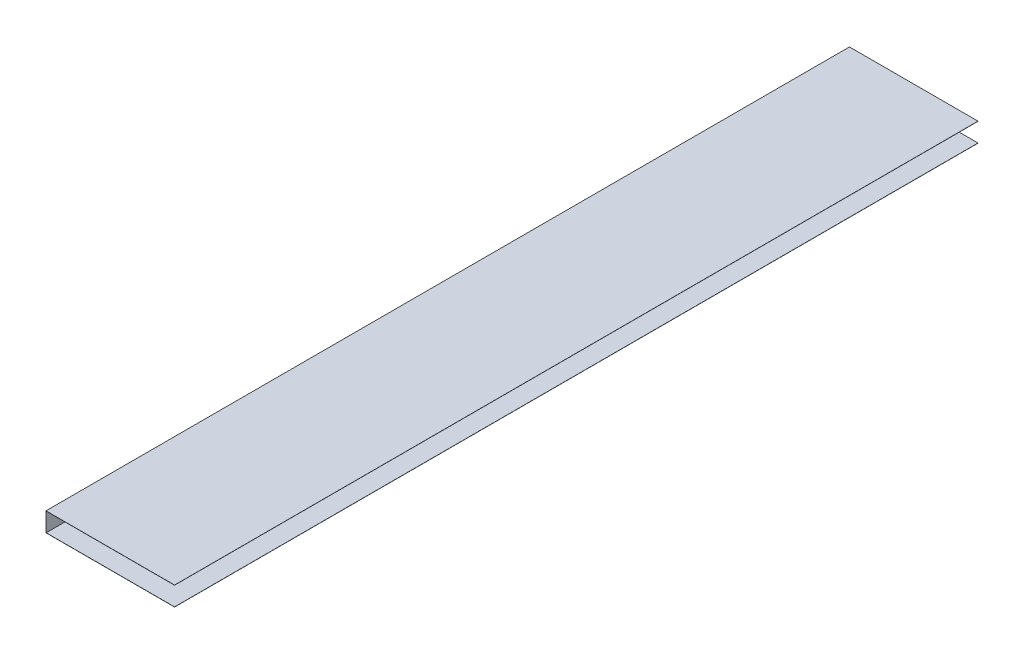
SolidWorks part; units mm, degrees
ref_plane "Front Plane" through (0, 0, 0) normal (0, 0, 1) x (1, 0, 0)
ref_plane "Top Plane" through (0, 0, 0) normal (0, 1, 0) x (1, 0, 0)
ref_plane "Right Plane" through (0, 0, 0) normal (1, 0, 0) x (0, 0, -1)
sketch "Sketch1" plane through (0, 0, 0) normal (0, 0, 1) x (1, 0, 0)
  line L0 (0, 0) -> (148, 0)
  line L1 (148, 0) -> (148, -0.2)
  line L2 (148, -0.2) -> (0.2, -0.2)
  line L3 (0.2, -0.2) -> (0.2, -21.8)
  line L4 (0.2, -21.8) -> (148, -21.8)
  line L5 (148, -21.8) -> (148, -22)
  line L6 (148, -22) -> (0, -22)
  line L7 (0, -22) -> (0, 0)
  point P3 (0, 0)
  point P10 (0, -11)
  dimension "D1" = 0.2
  dimension "D2" = 148
  dimension "D3" = 0.2
  dimension "D4" = 0.2
  dimension "D5" = 22
extrude "Boss-Extrude1" add sketch "Sketch1" along normal blind 925
equation "\"SlotHeight\"= 152mm"
equation "\"WedgeHeight\"= 4mm"
equation "\"PaperHeight\"= \"SlotHeight\" - \"WedgeHeight\""
equation "\"PaperThickness\"= 0.2mm"
equation "\"PaperWidth\"= 22mm"
equation "\"D1@Sketch1\"= \"PaperThickness\""
equation "\"D2@Sketch1\"= \"PaperHeight\""
equation "\"D3@Sketch1\"= \"PaperThickness\""
equation "\"D4@Sketch1\"= \"PaperThickness\""
equation "\"D5@Sketch1\" = \"PaperWidth\""
equation "\"AxialLength\"= 925mm"
equation "\"D1@Boss-Extrude1\"= \"AxialLength\""
